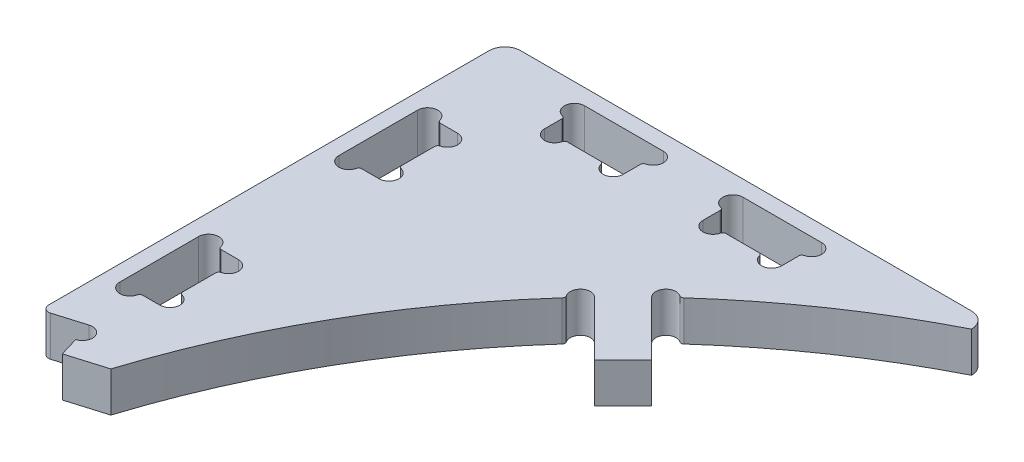
SolidWorks part; units mm, degrees
ref_plane "Front Plane" through (0, 0, 0) normal (0, 0, 1) x (1, 0, 0)
ref_plane "Top Plane" through (0, 0, 0) normal (0, 1, 0) x (1, 0, 0)
ref_plane "Right Plane" through (0, 0, 0) normal (1, 0, 0) x (0, 0, -1)
sketch "Sketch1" plane through (0, 0, 0) normal (0, 1, 0) x (1, 0, 0)
  line L0 (-172.1933, 181.2442) -> (-154.9271, 163.9781)
  line L1 (-112.6133, 223.2) -> (-112.6133, 228.2)
  line L2 (-112.6133, 228.2) -> (-265.7367, 228.2)
  line L3 (-265.7367, 228.2) -> (-265.7367, 80.6802)
  line L4 (-265.7367, 223.2) -> (-112.6133, 223.2) construction
  line L5 (-154.9271, 163.9781) -> (-163.9781, 154.9271)
  line L6 (-163.9781, 154.9271) -> (-181.2442, 172.1933)
  line L7 (-160.1567, 223.2) -> (-160.1567, 210.5)
  line L8 (-160.1567, 210.5) -> (-185.1567, 210.5)
  line L9 (-185.1567, 210.5) -> (-185.1567, 223.2)
  line L10 (-185.1567, 223.2) -> (-160.1567, 223.2)
  line L11 (-265.7367, 80.6802) -> (-253.7699, 84.2747)
  line L12 (-235.4467, 223.2) -> (-210.4467, 223.2)
  line L13 (-235.4467, 223.2) -> (-235.4467, 210.5)
  line L14 (-235.4467, 210.5) -> (-210.4467, 210.5)
  line L15 (-210.4467, 223.2) -> (-210.4467, 210.5)
  line L16 (-260.7367, 195.5) -> (-248.0367, 195.5)
  line L17 (-260.7367, 195.5) -> (-260.7367, 170.5)
  line L18 (-260.7367, 170.5) -> (-248.0367, 170.5)
  line L19 (-248.0367, 195.5) -> (-248.0367, 170.5)
  line L20 (-260.7367, 125.9748) -> (-248.0367, 125.9748)
  line L21 (-260.7367, 125.9748) -> (-260.7367, 100.9748)
  line L22 (-260.7367, 100.9748) -> (-248.0367, 100.9748)
  line L23 (-248.0367, 125.9748) -> (-248.0367, 100.9748)
  line L24 (-253.7699, 84.2747) -> (-250.1165, 72.1115)
  line L25 (-250.1165, 72.1115) -> (-238.2734, 75.6688)
  line L26 (-159.4526, 159.4526) -> (0, 0) construction
  circle A0 centre (0, 0) radius 250 construction
  arc A1 (-112.6133, 223.2) -> (-172.1933, 181.2442) centre (0, 0) ccw
  arc A2 (-181.2442, 172.1933) -> (-238.2734, 75.6688) centre (0, 0) ccw
  dimension "D2" = 500
  dimension "D1" = 5
  dimension "D3" = 12.8
  dimension "D4" = 12.7
  dimension "D5" = 147.5198
  dimension "D6" = 153.1233
  dimension "D7" = 30.29
  dimension "D8" = 25
  dimension "D9" = 25.29
  dimension "D10" = 25
  dimension "D11" = 27.7
  dimension "D12" = 5
  dimension "D13" = 25
  dimension "D14" = 12.7
  dimension "D15" = 12.7
  dimension "D16" = 44.5252
  dimension "D17" = 24.4181
  dimension "D18" = 71.7966
  dimension "D19" = 108.5788
  dimension "D20" = 12.4949
  dimension "D21" = 12.3658
  dimension "D22" = 12.7
extrude "Boss-Extrude1" add sketch "Sketch1" along normal blind 12.7
sketch "Sketch2" plane through (0, 12.7, 0) normal (0, 1, 0) x (1, 0, 0)
  line L0 (-185.1567, 210.5) -> (-160.1567, 210.5) construction
  line L1 (-160.1567, 210.5) -> (-160.1567, 223.2) construction
  line L2 (-185.1567, 223.2) -> (-185.1567, 210.5) construction
  line L3 (-210.4467, 210.5) -> (-210.4467, 223.2) construction
  line L4 (-235.4467, 210.5) -> (-210.4467, 210.5) construction
  line L5 (-235.4467, 223.2) -> (-235.4467, 210.5) construction
  line L6 (-248.0367, 195.5) -> (-260.7367, 195.5) construction
  line L7 (-248.0367, 170.5) -> (-248.0367, 195.5) construction
  line L8 (-260.7367, 170.5) -> (-248.0367, 170.5) construction
  line L9 (-248.0367, 125.9748) -> (-260.7367, 125.9748) construction
  line L10 (-260.7367, 100.9748) -> (-248.0367, 100.9748) construction
  line L11 (-248.0367, 100.9748) -> (-248.0367, 125.9748) construction
  line L12 (-253.7699, 84.2747) -> (-250.1165, 72.1115) construction
  circle A0 centre (-169.8593, 183.4334) radius 3.2
  arc A1 (-112.6133, 223.2) -> (-172.1933, 181.2442) centre (0, 0) ccw construction
  circle A2 centre (-183.4334, 169.8593) radius 3.2
  arc A3 (-181.2442, 172.1933) -> (-238.2734, 75.6688) centre (0, 0) ccw construction
  circle A4 centre (-181.9567, 210.5) radius 3.2
  circle A5 centre (-163.3567, 210.5) radius 3.2
  circle A6 centre (-160.1567, 220) radius 3.2
  circle A7 centre (-185.1567, 220) radius 3.2
  circle A8 centre (-210.4467, 220) radius 3.2
  circle A9 centre (-213.6467, 210.5) radius 3.2
  circle A10 centre (-232.2467, 210.5) radius 3.2
  circle A11 centre (-235.4467, 220) radius 3.2
  circle A12 centre (-257.5367, 195.5) radius 3.2
  circle A13 centre (-248.0367, 192.3) radius 3.2
  circle A14 centre (-248.0367, 173.7) radius 3.2
  circle A15 centre (-257.5367, 170.5) radius 3.2
  circle A16 centre (-257.5367, 125.9748) radius 3.2
  circle A17 centre (-257.5367, 100.9748) radius 3.2
  circle A18 centre (-248.0367, 104.1748) radius 3.2
  circle A19 centre (-248.0367, 122.7748) radius 3.2
  circle A20 centre (-252.8494, 81.2099) radius 3.2
  dimension "D1" = 6.4
extrude "Cut-Extrude1" cut sketch "Sketch2" against normal through all
fillet "Fillet1" radius 5 2 edges at (-112.6133, 6.35, -228.2) (-265.7367, 6.35, -228.2)
fillet "Fillet2" radius 1 18 edges at (-167.4975, 6.35, -185.5926) (-185.5926, 6.35, -167.4975) (-248.0367, 6.35, -107.3748) (-254.3367, 6.35, -100.9748) (-254.3367, 6.35, -125.9748) (-248.0367, 6.35, -119.5748) (-216.8467, 6.35, -210.5) (-229.0467, 6.35, -210.5) (-235.4467, 6.35, -216.8) (-160.1567, 6.35, -216.8) (-166.5567, 6.35, -210.5) (-178.7567, 6.35, -210.5) (-185.1567, 6.35, -216.8) (-210.4467, 6.35, -216.8) (-248.0367, 6.35, -189.1) (-248.0367, 6.35, -176.9) (-254.3367, 6.35, -170.5) (-254.3367, 6.35, -195.5)
fillet "Fillet3" radius 2 1 edges at (-265.7367, 6.35, -80.6802)
